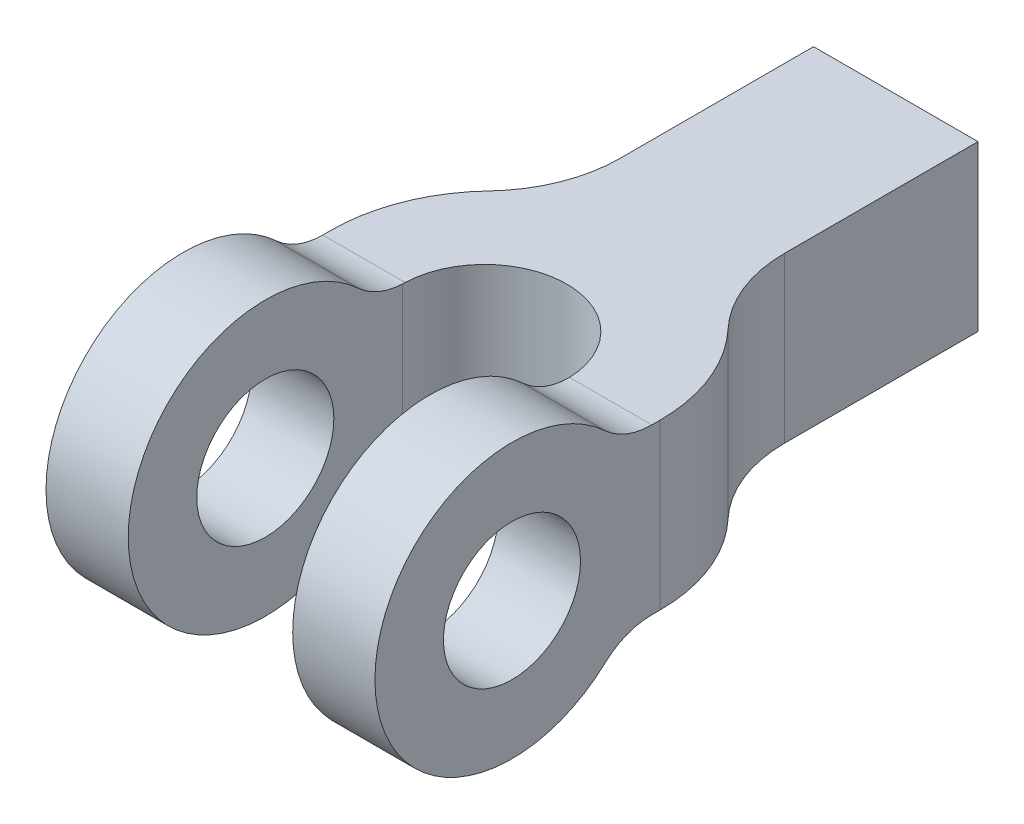
SolidWorks part; units mm, degrees
ref_plane "Front Plane" through (0, 0, 0) normal (0, 0, 1) x (1, 0, 0)
ref_plane "Top Plane" through (0, 0, 0) normal (0, 1, 0) x (1, 0, 0)
ref_plane "Right Plane" through (0, 0, 0) normal (1, 0, 0) x (0, 0, -1)
sketch "Sketch1" plane through (0, 0, 0) normal (0, 1, 0) x (1, 0, 0)
  line L1 (0, 0) -> (-1200, 0)
  line L2 (0, 0) -> (0, 2500)
  line L3 (0, 2500) -> (-1200, 2500)
  line L4 (-1200, 0) -> (-1200, 2500)
  dimension "D1" = 1200
  dimension "D2" = 2500
extrude "Boss-Extrude1" add sketch "Sketch1" along normal blind 1000
sketch "Sketch2" plane through (0, 1000, 0) normal (0, 1, 0) x (1, 0, 0)
  line L0 (-600, 2500) -> (-600, 0) construction
  line L1 (0, 2500) -> (-1200, 2500) construction
  line L2 (-1200, 0) -> (0, 0) construction
  line L3 (-900, 2500) -> (-900, 1794.9834)
  line L4 (-300, 2500) -> (-300, 1794.9834)
  line L5 (-900, 1000) -> (-900, 0)
  line L6 (-300, 1000) -> (-300, 0)
  line L9 (0, 0) -> (0, 2500)
  line L10 (0, 2500) -> (-1200, 2500)
  line L11 (-1200, 2500) -> (-1200, 0)
  line L12 (-1200, 0) -> (0, 0)
  line L13 (0, 0) -> (0, 2500)
  line L14 (0, 2500) -> (-1200, 2500)
  line L15 (-1200, 2500) -> (-1200, 0)
  line L16 (-1200, 0) -> (0, 0)
  arc A0 (-300, 1000) -> (-900, 1000) centre (-600, 1000) ccw
  arc A1 (-1036.3636, 1451.8092) -> (-163.6364, 1451.8092) centre (-600, 1040) ccw
  arc A2 (-300, 1794.9834) -> (-163.6364, 1451.8092) centre (200, 1794.9834) ccw
  arc A3 (-900, 1794.9834) -> (-1036.3636, 1451.8092) centre (-1400, 1794.9834) cw
  point P18 (-300, 1559.6152)
  point P22 (-900, 1559.6152)
  line M12 (0, 2500) -> (-1200, 2500)
  line M13 (-1200, 2500) -> (-1200, 0)
  line M14 (-1200, 0) -> (0, 0)
  dimension "D1" = 600
  dimension "D2" = 1200
  dimension "D4" = 1500
  dimension "D7" = 500
  dimension "D3" = 40
  dimension "D5" = 300
  dimension "D6" = 0
extrude "Cut-Extrude1" cut sketch "Sketch2" against normal through all contours A3 L3 A1 M12 M13 | L4 A2 A1 L13 M12 | L0 A0 L5 A1 | A0 L0 A1 L6 | L0 A1 L5 M14 | A1 L0 L16 L6 region at (-459.5149, 1000, -853.3741) region at (-740.4851, 1000, -853.3741) region at (-138.2519, 1000, -1955.027) region at (-1061.7481, 1000, -1955.027) region at (-445.7522, 1000, -233.6195) region at (-754.2478, 1000, -233.6195)
sketch "Sketch3" plane through (0, 0, 0) normal (1, 0, 0) x (0, 0, -1)
  line L0 (0, 1000) -> (1040, 1000) construction
  line L1 (0, 1000) -> (0, 0) construction
  line L2 (0, 0) -> (1040, 0) construction
  line L3 (500, 500) -> (2500, 500) construction
  line L4 (2500, 0) -> (2500, 1000) construction
  line L5 (1040, 0) -> (1451.8092, 0) construction
  line L6 (2500, 800) -> (1009.902, 800)
  line L7 (2500, 800) -> (2500, 200)
  line L8 (2500, 200) -> (1009.902, 200)
  line L10 (1451.8092, 0) -> (1794.9834, 0) construction
  line L11 (2500, 0) -> (1794.9834, 0) construction
  line L12 (2500, 1000) -> (1794.9834, 1000) construction
  line L13 (1794.9834, 1000) -> (1451.8092, 1000) construction
  line L14 (1451.8092, 1000) -> (1040, 1000) construction
  line L15 (0, 1000) -> (0, 0)
  line L16 (0, 1000) -> (1040, 1000)
  line L17 (0, 0) -> (1040, 0)
  line L18 (1040, 0) -> (1451.8092, 0)
  line L19 (1451.8092, 0) -> (1794.9834, 0)
  line L20 (2500, 0) -> (1794.9834, 0)
  line L21 (2500, 0) -> (2500, 1000)
  line L22 (2500, 1000) -> (1794.9834, 1000)
  line L23 (1794.9834, 1000) -> (1451.8092, 1000)
  line L24 (1451.8092, 1000) -> (1040, 1000)
  arc A0 (839.9346, 866.6667) -> (839.9346, 133.3333) centre (500, 500) ccw
  circle A1 centre (500, 500) radius 250
  arc A2 (1009.902, 200) -> (839.9346, 133.3333) centre (1009.902, -50) ccw
  arc A3 (839.9346, 866.6667) -> (1009.902, 800) centre (1009.902, 1050) ccw
  line M9 (0, 0) -> (1040, 0)
  line M10 (1040, 0) -> (1040, 1000)
  line M11 (1040, 1000) -> (0, 1000)
  line M12 (0, 1000) -> (0, 0)
  dimension "D1" = 500
  dimension "D3" = 250
  dimension "D2" = 600
extrude "Cut-Extrude2" cut sketch "Sketch3" against normal through all contours A0 L16 M12 | A0 A3 L6 M10 M11 | L23 L24 L6 L21 L22 M10 | A0 L15 M9 | L8 A2 A0 L17 M10 | L20 L21 L8 L18 L19 M10 | A1 region at (0, 900, -1770) region at (0, 922.7719, -892.915) region at (0, 100, -1770) region at (0, 77.2281, -892.915) region at (0, 888.316, -111.684) region at (0, 111.684, -111.684) region at (0, 500, -500)
